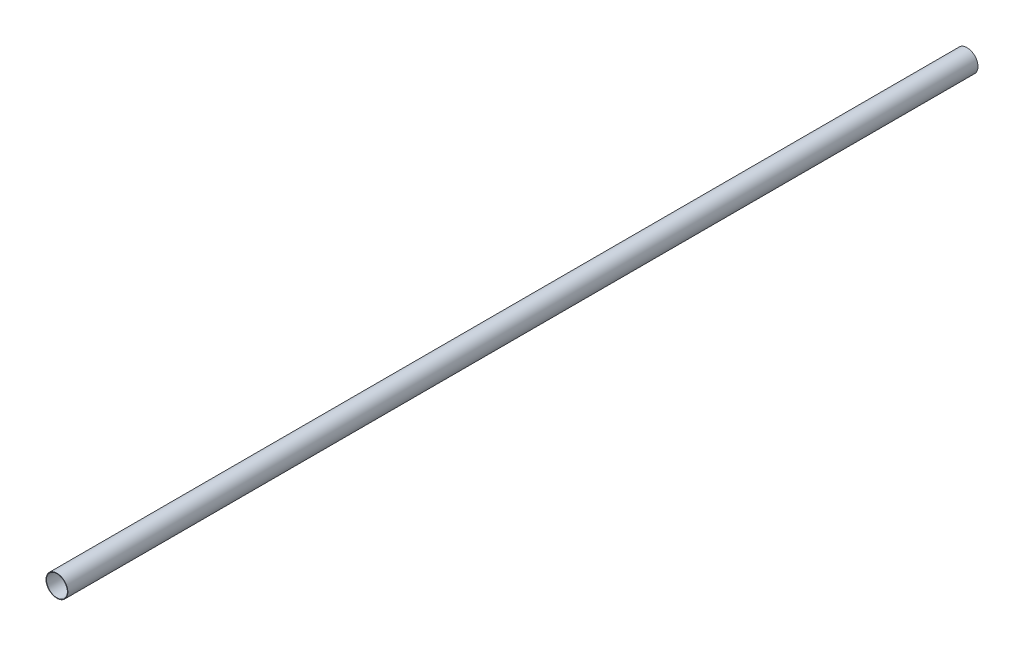
SolidWorks part; units mm, degrees
ref_plane "Front Plane" through (0, 0, 0) normal (0, 0, 1) x (1, 0, 0)
ref_plane "Top Plane" through (0, 0, 0) normal (0, 1, 0) x (1, 0, 0)
ref_plane "Right Plane" through (0, 0, 0) normal (1, 0, 0) x (0, 0, -1)
sketch "Sketch1" plane through (0, 0, 0) normal (0, 0, 1) x (1, 0, 0)
  circle A0 centre (0, 0) radius 15
  circle A1 centre (0, 0) radius 14.35
  dimension "D1" = 30
  dimension "D2" = 28.7
extrude "Boss-Extrude1" add sketch "Sketch1" along normal blind 1250
